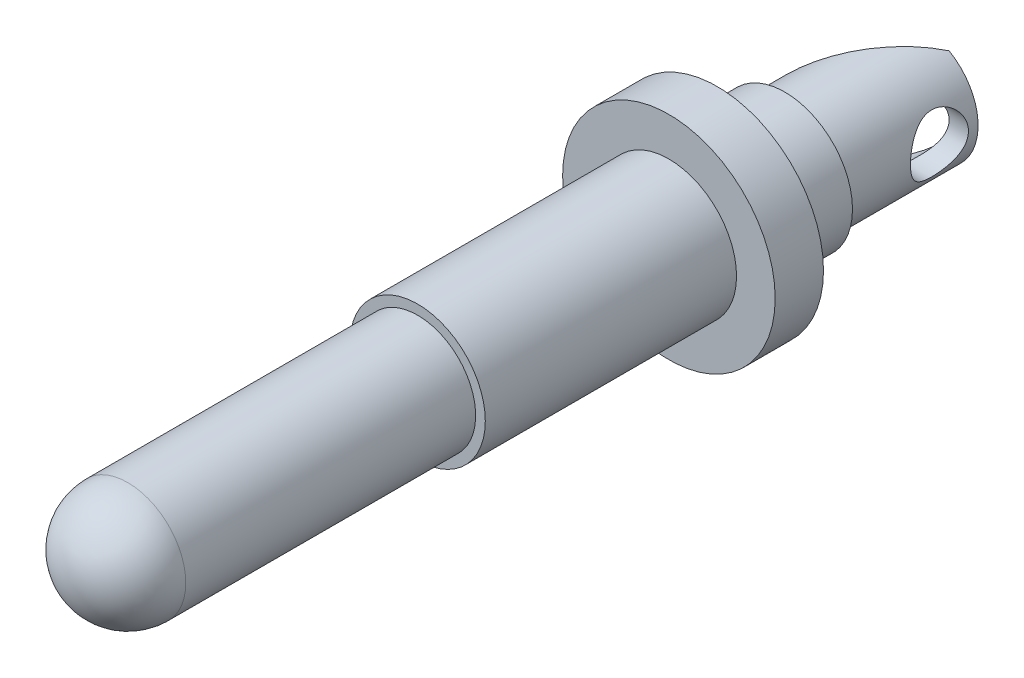
SolidWorks part; units mm, degrees
material "Латунь"
ref_plane "Спереди" through (0, 0, 0) normal (0, 0, 1) x (1, 0, 0)
ref_plane "Сверху" through (0, 0, 0) normal (0, 1, 0) x (1, 0, 0)
ref_plane "Справа" through (0, 0, 0) normal (1, 0, 0) x (0, 0, -1)
sketch "Эскиз1" plane through (0, 0, 0) normal (0, 0, 1) x (1, 0, 0)
  circle A0 centre (0, 0) radius 3
  dimension "D1" = 6
extrude "Бобышка-Вытянуть1" add sketch "Эскиз1" along normal blind 15
dome "Купол1" faces to dome 1 distance 3 reverse direction no elliptical dome no face at (3, 0, 15) parameters "D1"=3
sketch "Эскиз4" plane through (0, 0, 0) normal (0, 0, -1) x (-1, 0, 0)
  circle A0 centre (0, 0) radius 3.5
  dimension "D1" = 7
extrude "Бобышка-Вытянуть2" add sketch "Эскиз4" along normal blind 26
sketch "Эскиз5" plane through (0, 0, -26) normal (0, 0, -1) x (-1, 0, 0)
  circle A0 centre (0, 0) radius 3
  circle A1 centre (0, 0) radius 3.5 construction
  circle A2 centre (0, 0) radius 3.5
  dimension "D1" = 6
extrude "Вырез-Вытянуть3" cut sketch "Эскиз5" against normal blind 7
sketch "Эскиз6" plane through (0, 0, 0) normal (0, 0, 1) x (1, 0, 0)
  circle A0 centre (0, 0) radius 5.5
  dimension "D1" = 11
extrude "Бобышка-Вытянуть3" add sketch "Эскиз6" against normal blind 2.5 from offset 13 offset against normal yes
hole_wizard "Диаметр отверстия Ø4.0 (4)1" positions "Трехмерный эскиз1" profile "Эскиз7" hole size "Ø4.0" standard "Ansi Metric"
sketch3d "Трехмерный эскиз1"
  line L0 (0, 0, -19) -> (0, 0, -26) construction
  point P0 (0, 0, -26)
sketch "Эскиз7" plane through (0, 0, -26) normal (1, 0, 0) x (0, 1, 0)
  line L0 (0, 0) -> (0, 8.7017)
  line L1 (0, 8.7017) -> (2, 7.5)
  line L2 (2, 7.5) -> (2, 0)
  line L5 (2, 0) -> (0, 0)
  line L10 (0, 8.7017) -> (-2, 7.5) construction
  line L11 (0, -6.35) -> (0, 107.95) construction
  dimension "Диаметр отверстия" = 4
  dimension "Глубина отверстия" = 7.5
  dimension "Угол заточки сверла" = 118
sketch "Эскиз9" plane through (0, 0, 0) normal (0, 1, 0) x (1, 0, 0)
  line L0 (2, 26) -> (-2, 26) construction
  line L1 (-3, 26) -> (-3, 19) construction
  point P0 (-3, 24)
  dimension "D1" = 2
hole_wizard "Диаметр отверстия Ø3.0 (3)1" positions "Трехмерный эскиз3" profile "Эскиз11" hole size "Ø3.0" standard "Ansi Metric"
sketch3d "Трехмерный эскиз3"
  point P0 (-3, 0, -24)
  point P4 (-3, 0, -24)
sketch "Эскиз11" plane through (-3, 0, -24) normal (0, 1, 0) x (0, 0, 1)
  line L0 (0, 0) -> (0, 9.9013)
  line L1 (0, 9.9013) -> (1.5, 9)
  line L2 (1.5, 9) -> (1.5, 0)
  line L5 (1.5, 0) -> (0, 0)
  line L10 (0, 9.9013) -> (-1.5, 9) construction
  line L11 (0, -6.35) -> (0, 107.95) construction
  dimension "Диаметр отверстия" = 3
  dimension "Глубина отверстия" = 9
  dimension "Угол заточки сверла" = 118
sketch "Эскиз12" plane through (0, 0, 0) normal (0, 1, 0) x (1, 0, 0)
  line L0 (1.5, 26) -> (-3, 20)
  line L1 (3, 26) -> (-3, 26) construction
  line L2 (-3, 20) -> (-3, 26)
  line L3 (-3, 26) -> (1.5, 26)
  dimension "D1" = 1.5
  dimension "D2" = 6
extrude "Вырез-Вытянуть4" cut sketch "Эскиз12" against normal through all and the other way through all
